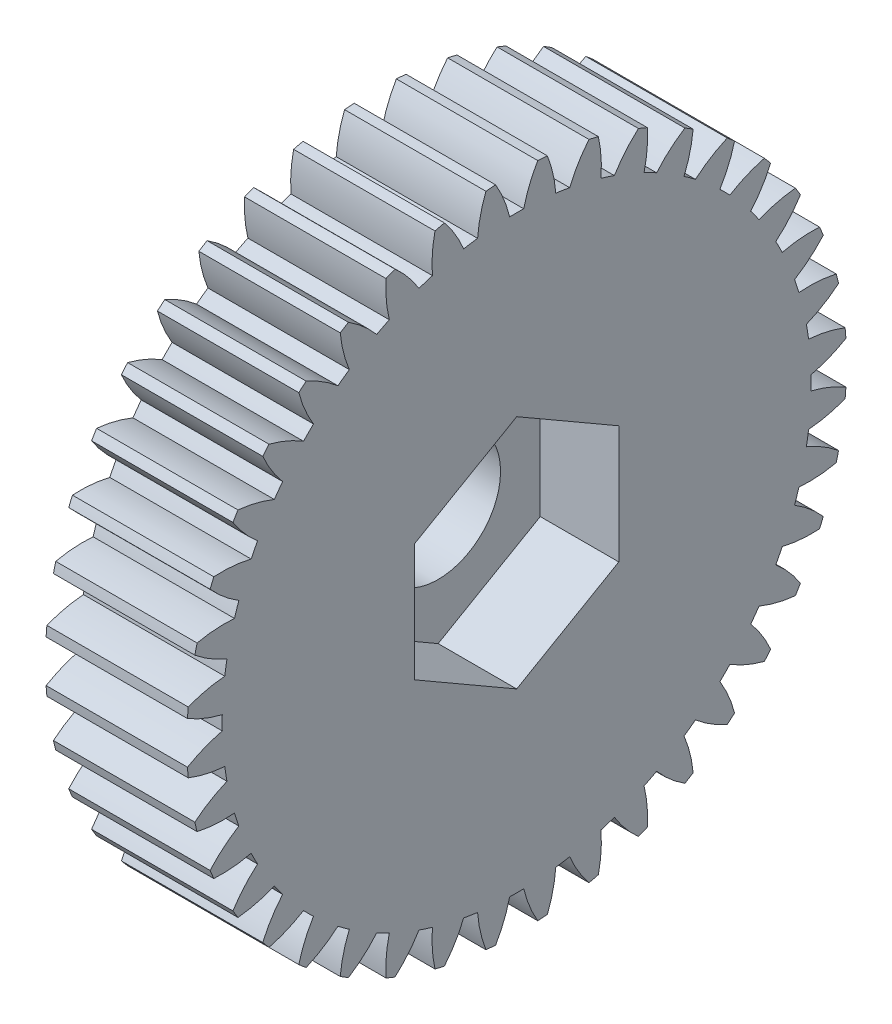
SolidWorks part; units mm, degrees
ref_plane "Plane1" through (0, 0, 0) normal (0, 0, 1) x (1, 0, 0)
ref_plane "Plane2" through (0, 0, 0) normal (0, 1, 0) x (1, 0, 0)
ref_plane "Plane3" through (0, 0, 0) normal (1, 0, 0) x (0, 0, -1)
sketch "HoldingSke" plane through (0, 0, 0) normal (0, 1, 0) x (1, 0, 0)
  line L0 (0, 0) -> (0.766, -0.6428)
  line L1 (-15, 0) -> (100, 0) construction
  line L2 (0, 0) -> (-2.1039, 2.3779)
  line L3 (0, 0) -> (-11.863, 4.5341)
  line L4 (0, 0) -> (6.6156, 5.5511)
  line L5 (0, 0) -> (-46.8476, -17.4728)
  line L6 (0, 0) -> (-7.4607, -5.0337)
  line L7 (-2.1039, 2.3779) -> (8.6586, 51.2059)
  line L8 (-76.2, 54.61) -> (-75.5, 54.61)
  line L9 (-71.009, 38.7566) -> (-53.1078, 45.2721)
  line L10 (-76.2, 71.12) -> (104.1128, 71.12)
  line L11 (0, 0) -> (-9, 0)
  line L12 (-76.2, 101.6) -> (-76.162, 101.6)
  line L13 (24.9733, 27.94) -> (52.9518, 28.4284)
  line L14 (24.9733, 27.94) -> (24.9743, 27.94)
  line L15 (24.9733, 27.94) -> (100.4006, 29.5858)
  line L16 (-63.627, -1) -> (-12.827, -1)
  circle A0 centre (0, 0) radius 2
  circle A1 centre (0, 0) radius 18.749
  circle A2 centre (0, 0) radius 37.5
  circle A3 centre (0, 0) radius 2
  dimension "MHD" = 37.498
  dimension "Hub_dia" = 75
  dimension "Bore" = 4
  dimension "MBD" = 4
  dimension "Num_teeth" = 40
  dimension "Pitch" = 1
  dimension "Overall_len" = 50
  dimension "Show_teeth" = 40
  dimension "Thickness" = 9
  dimension "OAL" = 50.0001
  dimension "T_dim" = 0.7
  dimension "Ap" = 20
  dimension "H" = 19.05
  dimension "Pitch_radius" = 180.3128
  dimension "Width" = 9
  dimension "Backlash" = 0.038
  dimension "Addendum_fac" = 1
  dimension "Dedendum_fac" = 1.25
  dimension "Clearance_fac" = 0.25
  dimension "Dedendum_add" = 0.001
  dimension "Module" = 1
sketch "BasProSke" plane through (0, 0, 0) normal (0, 1, 0) x (1, 0, 0)
  line L0 (-10, 0) -> (60, 0) construction
  line L1 (0, 0) -> (0, 21)
  line L2 (0, 0) -> (9, 0)
  line L3 (9, 0) -> (9, 21)
  line L4 (9, 21) -> (0, 21)
  dimension "Thickness" = 9
  dimension "Diameter" = 42
revolve "Base-Revolve" add sketch "BasProSke" angle 360 about L0
sketch "TooCutSke" plane through (0, 0, 0) normal (1, 0, 0) x (0, 0, -1)
  line L1 (0, 0) -> (0, 107) construction
  line L2 (0, 0) -> (-0.8517, 19.9819) construction
  line L3 (0, 0) -> (-3.1363, 39.8509) construction
  line L4 (-0.8517, 19.9819) -> (-1.5682, 19.9255) construction
  arc A0 (0.4487, 18.7436) -> (-0.4487, 18.7436) centre (0, 0) ccw
  arc A1 (1.3547, 20.9817) -> (-1.3547, 20.9817) centre (0, 0) ccw
  circle A2 centre (0, 0) radius 20 construction
  circle A3 centre (0, 0) radius 18.7939 construction
  arc A4 (-0.4487, 18.7436) -> (-1.3547, 20.9817) centre (-8.2322, 16.895) ccw
  arc A5 (1.3547, 20.9817) -> (0.4487, 18.7436) centre (8.2322, 16.895) ccw
  dimension "Root_dia" = 37.498
  dimension "Overcut_dia" = 42.0508
  dimension "Pitch_dia" = 40
  dimension "Base_dia" = 37.5877
  dimension "Flank_rad" = 8
  dimension "Half_ang" = 4.5
  dimension "Half_CT" = 0.7187
extrude "ToothCut" cut sketch "TooCutSke" along normal through all
fillet "Breaks" [suppressed] radius 0.02 tangent propagation no
fillet "RootFillets" [suppressed] radius 0.251
pattern_circular "TeethCuts" count 40 every 9 about axis through (-10, 0, 0) along (1, 0, 0) of "ToothCut", "RootFillets", "Breaks"
sketch "HubNeaOneSke" plane through (0, 0, 0) normal (-1, 0, 0) x (0, 0, 1)
  circle A0 centre (0, 0) radius 18.749
  dimension "Diameter" = 37.498
extrude "HubNearOne" [suppressed] add sketch "HubNeaOneSke" along normal blind 41.0001
sketch "HubNeaBotSke" plane through (0, 0, 0) normal (-1, 0, 0) x (0, 0, 1)
  circle A0 centre (0, 0) radius 18.749
  dimension "Diameter" = 37.498
extrude "HubNearBoth" [suppressed] add sketch "HubNeaBotSke" along normal blind 20.5
ref_plane "FarPln" through (9, 0, 0) normal (1, 0, 0) x (0, 0, -1)
sketch "HubFarSke" plane through (9, 0, 0) normal (1, 0, 0) x (0, 0, -1)
  circle A0 centre (0, 0) radius 18.749
  dimension "Diameter" = 37.498
extrude "HubFar" [suppressed] add sketch "HubFarSke" along normal blind 20.5
sketch "BorSke" plane through (0, 0, 0) normal (1, 0, 0) x (0, 0, -1)
  circle A0 centre (0, 0) radius 2
  dimension "Diameter" = 4
extrude "Bore" cut sketch "BorSke" along normal mid plane 100.0001
sketch "KeySke" plane through (0, 0, 0) normal (1, 0, 0) x (0, 0, -1)
  line L0 (-0.8, 0) -> (-0.8, 2.7)
  line L1 (-0.8, 2.7) -> (0.8, 2.7)
  line L2 (0.8, 2.7) -> (0.8, 0)
  line L3 (0, 0) -> (0, 34) construction
  line L4 (-0.8, 0) -> (0.8, 0)
  dimension "Offset" = 2.7
  dimension "Width" = 1.6
extrude "Keyway" [suppressed] cut sketch "KeySke" along normal mid plane 100.0001
pattern_circular "Keyway2" [suppressed] count 2 every 90 about axis through (-10, 0, 0) along (1, 0, 0) reverse direction yes
sketch "Sketch1" plane through (9, 0, 0) normal (1, 0, 0) x (0, 0, -1)
  line L1 (0, 7.5056) -> (-6.5, 3.7528)
  line L2 (-6.5, 3.7528) -> (-6.5, -3.7528)
  line L3 (-6.5, -3.7528) -> (0, -7.5056)
  line L4 (0, -7.5056) -> (6.5, -3.7528)
  line L5 (6.5, -3.7528) -> (6.5, 3.7528)
  line L6 (6.5, 3.7528) -> (0, 7.5056)
  circle A0 centre (0, 0) radius 7.5056
  circle A2 centre (0, 0) radius 6.5 construction
  circle A3 centre (0, 0) radius 3.9725
  dimension "D1" = 7.945
  dimension "D2" = 13
extrude "Cut-Extrude1" cut sketch "Sketch1" against normal blind 5 contours L1 L2 L3 L4 L5 L6
extrude "Cut-Extrude2" cut sketch "Sketch1<7>" against normal through all contours A3 region at (9, 0, 0)
sketch "Sketch1<7>" plane through (9, 0, 0) normal (1, 0, 0) x (0, 0, -1) same geometry as "Sketch1"
sketch "Sketch2" plane through (0, 0, 0) normal (-1, 0, 0) x (0, 0, 1)
  circle A0 centre (0, 0) radius 6
  circle A1 centre (0, 0) radius 4
  dimension "D1" = 12
  dimension "D2" = 8
extrude "Boss-Extrude1" add sketch "Sketch2" along normal blind 1.3
equation "' \"Module@HoldingSke\" = 6.35"
equation "' \"Num_teeth@HoldingSke\" = 12"
equation "' \"Ap@HoldingSke\" =  20"
equation "' \"Ap@HoldingSke\" = 20"
equation "' \"Width@HoldingSke\" = 0.5 * 25.4"
equation "' \"Hub_dia@HoldingSke\"= 1 * 25.4"
equation "' \"Hub_dia@HoldingSke\" = 1 * 25.4"
equation "' \"Overall_len@HoldingSke\" = 1.0 * 25.4"
equation "' \"Bore@HoldingSke\" = 0.75 * 25.4"
equation "' \"T_dim@HoldingSke\" = 0.1 * 25.4"
equation "' \"Width@KeySke\" = 0.25 * 25.4"
equation "' \"Show_teeth@HoldingSke\" = 13"
equation "' \"Backlash@HoldingSke\" = 0.009 * 25.4"
equation "' \"Addendum_fac@HoldingSke\" = 1.0"
equation "' \"Dedendum_fac@HoldingSke\" = 1.25"
equation "' \"Dedendum_add@HoldingSke\" = 0.00005 * 25.4"
equation "' \"Clearance_fac@HoldingSke\" = 0.25"
equation "\"Pitch@HoldingSke\" = 1 / \"Module@HoldingSke\""
equation "\"Overcut_dia@TooCutSke\" = (\"Num_teeth@HoldingSke\" + 2 * \"Addendum_fac@HoldingSke\") / \"Pitch@HoldingSke\" + 0.002 * 25.4"
equation "\"Pitch_dia@TooCutSke\" = \"Num_teeth@HoldingSke\" / \"Pitch@HoldingSke\""
equation "\"Base_dia@TooCutSke\" = \"Num_teeth@HoldingSke\" / \"Pitch@HoldingSke\" * cos((\"Ap@HoldingSke\"  * 3.14159265 / 180))"
equation "\"Root_dia@TooCutSke\" = (\"Num_teeth@HoldingSke\" + 2) / \"Pitch@HoldingSke\" - 2 * (\"Addendum_fac@HoldingSke\" + \"Dedendum_fac@HoldingSke\") / \"Pitch@HoldingSke\" - \"Dedendum_add@HoldingSke\" * 2"
equation "\"Half_ang@TooCutSke\" = 180 / \"Num_teeth@HoldingSke\""
equation "\"Half_CT@TooCutSke\" = \"Num_teeth@HoldingSke\" / \"Pitch@HoldingSke\" * sin((3.14159265 / 2 / \"Num_teeth@HoldingSke\")) / 2 - 7 * \"Backlash@HoldingSke\" / 4"
equation "\"Flank_rad@TooCutSke\" = \"Num_teeth@HoldingSke\" / \"Pitch@HoldingSke\" / 5"
equation "\"Radius@RootFillets\" = \"Clearance_fac@HoldingSke\" / \"Pitch@HoldingSke\" + \"Dedendum_add@HoldingSke\""
equation "\"Break_rad@Breaks\" = 0.02 / \"Pitch@HoldingSke\""
equation "\"Thickness@HoldingSke\" = \"Width@HoldingSke\""
equation "\"OAL@HoldingSke\" = \"Thickness@HoldingSke\""
equation "\"MHD@HoldingSke\" = (\"Num_teeth@HoldingSke\" + 2) / \"Pitch@HoldingSke\" - 2 * (\"Addendum_fac@HoldingSke\" + \"Dedendum_fac@HoldingSke\")  / \"Pitch@HoldingSke\" - \"Dedendum_add@HoldingSke\" * 2"
equation "\"MBD@HoldingSke\" = (\"Num_teeth@HoldingSke\" + 2) / \"Pitch@HoldingSke\" - 2 * (\"Addendum_fac@HoldingSke\" + \"Dedendum_fac@HoldingSke\")  / \"Pitch@HoldingSke\" - \"Dedendum_add@HoldingSke\" * 2 - 0.002 * 25.4"
equation "\"MHD@HoldingSke\" = ((sgn( \"MHD@HoldingSke\" - \"Hub_dia@HoldingSke\" )-1)*( \"MHD@HoldingSke\" - \"Hub_dia@HoldingSke\" ))/-2+ \"Hub_dia@HoldingSke\""
equation "\"MBD@HoldingSke\" = ((sgn( \"MBD@HoldingSke\" - \"Bore@HoldingSke\" )-1)*( \"MBD@HoldingSke\" - \"Bore@HoldingSke\" ))/-2+ \"Bore@HoldingSke\""
equation "\"OAL@HoldingSke\" = ((sgn( \"OAL@HoldingSke\" - \"Overall_len@HoldingSke\" )+1)*( \"OAL@HoldingSke\" - \"Overall_len@HoldingSke\" ))/2 + \"Overall_len@HoldingSke\" + 0.000002 * 25.4"
equation "\"Num_teeth@TeethCuts\" = int( \"Show_teeth@HoldingSke\" ) + 1"
equation "\"Num_teeth@TeethCuts\" = ((sgn( \"Num_teeth@TeethCuts\" - \"Num_teeth@HoldingSke\" )-1)*( \"Num_teeth@TeethCuts\" - \"Num_teeth@HoldingSke\" ))/-2+ \"Num_teeth@HoldingSke\""
equation "\"Num_teeth@TeethCuts\" = ((sgn( \"Num_teeth@TeethCuts\" - 2.0)+1)*( \"Num_teeth@TeethCuts\" - 2.0))/2 +2.0"
equation "\"Angle@TeethCuts\" = 360.0 / \"Num_teeth@HoldingSke\""
equation "\"Diameter@BasProSke\" = (\"Num_teeth@HoldingSke\" + 2 * \"Addendum_fac@HoldingSke\") / \"Pitch@HoldingSke\""
equation "\"Thickness@BasProSke\"  = \"Thickness@HoldingSke\""
equation "' \"Fillet_rad@BasProSke\" =  \"Thickness@HoldingSke\" * 0.05"
equation "' \"Fillet_rad@BasProSke\" = \"Thickness@HoldingSke\" * 0.05"
equation "\"MHD@HoldingSke\" = ((sgn( \"MHD@HoldingSke\" - \"Root_dia@TooCutSke\" )-1)*( \"MHD@HoldingSke\" - \"Root_dia@TooCutSke\" ))/-2+ \"Root_dia@TooCutSke\""
equation "\"Diameter@HubNeaOneSke\" = \"MHD@HoldingSke\""
equation "\"Length@HubNearOne\" = \"OAL@HoldingSke\" - \"Thickness@BasProSke\""
equation "\"Diameter@HubNeaBotSke\" = \"MHD@HoldingSke\""
equation "\"Length@HubNearBoth\" = ( \"OAL@HoldingSke\" - \"Thickness@BasProSke\" ) / 2.0"
equation "\"Thickness@FarPln\" = \"Thickness@BasProSke\""
equation "\"Diameter@HubFarSke\" = \"MHD@HoldingSke\""
equation "\"Length@HubFar\" = ( \"OAL@HoldingSke\" - \"Thickness@BasProSke\" ) / 2.0"
equation "\"Diameter@BorSke\" = \"MBD@HoldingSke\""
equation "\"D1@Bore\" = \"OAL@HoldingSke\" * 2.0"
equation "\"D1@Keyway\" = \"OAL@HoldingSke\" * 2.0"
equation "\"Offset@KeySke\" = \"T_dim@HoldingSke\" + \"MBD@HoldingSke\" / 2.0"
